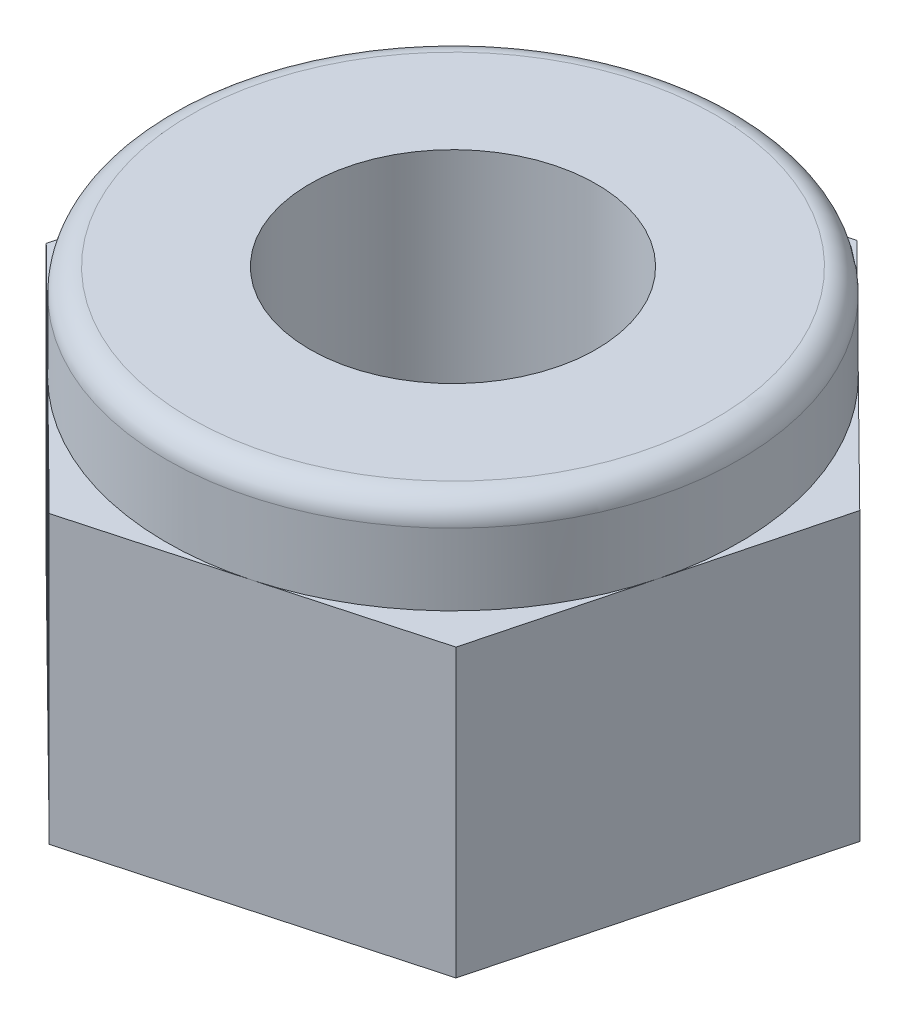
SolidWorks part; units mm, degrees
ref_plane "Front Plane" through (0, 0, 0) normal (0, 0, 1) x (1, 0, 0)
ref_plane "Top Plane" through (0, 0, 0) normal (0, 1, 0) x (1, 0, 0)
ref_plane "Right Plane" through (0, 0, 0) normal (1, 0, 0) x (0, 0, -1)
ref_axis "Axis1" through (0, -55, 0) along (0, 1, 0)
sketch "Sketch1" plane through (0, 0, 0) normal (0, 1, 0) x (1, 0, 0)
  line L1 (2.4652, -2.4337) -> (3.3402, 0.9181)
  line L2 (3.3402, 0.9181) -> (0.875, 3.3518)
  line L3 (0.875, 3.3518) -> (-2.4652, 2.4337)
  line L4 (-2.4652, 2.4337) -> (-3.3402, -0.9181)
  line L5 (-3.3402, -0.9181) -> (-0.875, -3.3518)
  line L6 (-0.875, -3.3518) -> (2.4652, -2.4337)
  circle A0 centre (0, 0) radius 3 construction
  dimension "D1" = 6
extrude "Boss-Extrude1" add sketch "Sketch1" along normal blind 3
sketch "Sketch3" plane through (0, 3, 0) normal (0, 1, 0) x (1, 0, 0)
  circle A0 centre (0, 0) radius 3
  dimension "D1" = 6
extrude "Boss-Extrude2" add sketch "Sketch3" along normal blind 1
sketch "Sketch4" plane through (0, 4, 0) normal (0, 1, 0) x (1, 0, 0)
  circle A0 centre (0, 0) radius 1.5
  dimension "D1" = 3
extrude "Cut-Extrude1" cut sketch "Sketch4" against normal up to next
fillet "Fillet1" radius 0.25 1 edges at (0, 4, 3)
